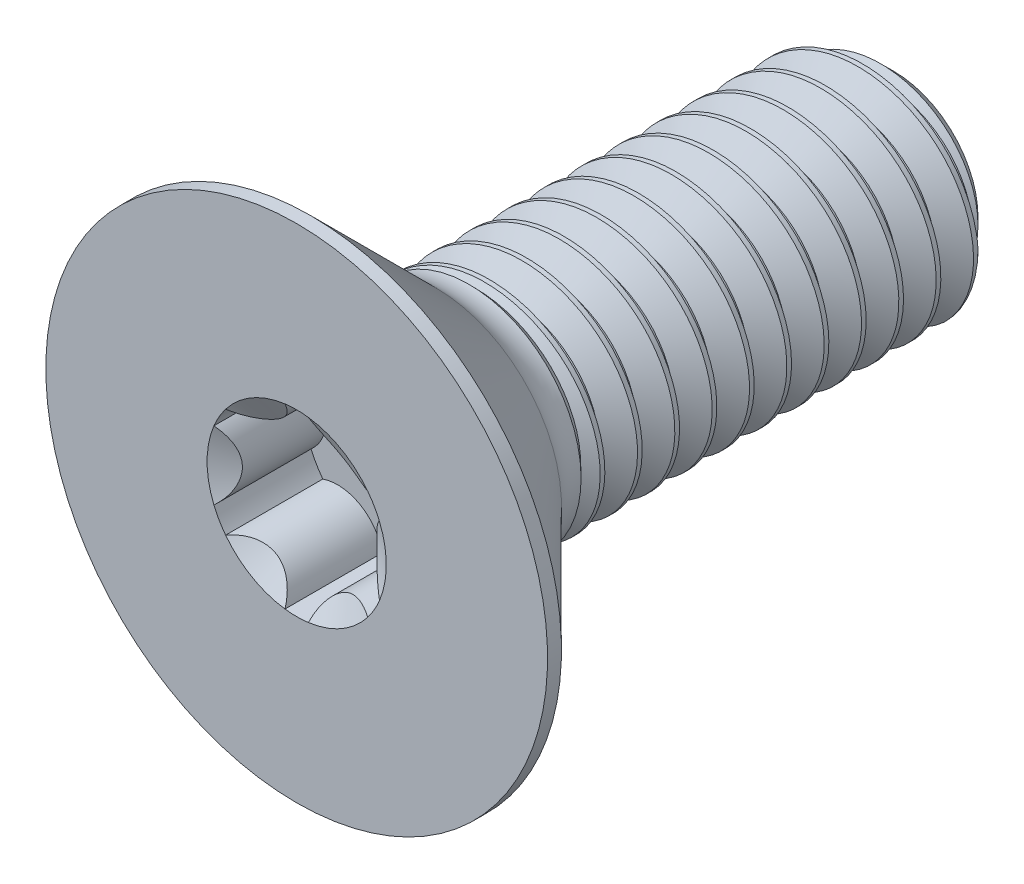
SolidWorks part; units mm, degrees
ref_plane "Front" through (0, 0, 0) normal (0, 0, 1) x (1, 0, 0)
ref_plane "Top" through (0, 0, 0) normal (0, 1, 0) x (1, 0, 0)
ref_plane "Right" through (0, 0, 0) normal (1, 0, 0) x (0, 0, -1)
sketch "Sketch1" plane through (0, 0, 0) normal (1, 0, 0) x (0, 0, -1)
  line L0 (0, 3.36) -> (0.186, 3.36) construction
  line L1 (0.186, 3.36) -> (1.86, 1.686) construction
  line L2 (0, 1.5) -> (8, 1.5)
  line L3 (8, 1.5) -> (8, 0)
  line L4 (8, 0) -> (0, 0)
  line L5 (0, 0) -> (0, 3.36) construction
  line L6 (0, 3.36) -> (0, -3.36) construction
  line L7 (8, 1.5) -> (8, -1.5) construction
  line L8 (0, -3.36) -> (0.186, -3.36) construction
  line L9 (0.186, -3.36) -> (1.86, -1.686) construction
  line L11 (0, 1.5) -> (0, 0)
  line L12 (2.309, 1.5) -> (2.309, 0) construction
  arc A1 (1.86, 1.686) -> (2.309, 1.5) centre (2.309, 2.135) ccw construction
  dimension "D1" = 0.186
revolve "Revolve1" add sketch "Sketch1" angle 360 mid plane about L4
sketch "Sketch3" plane through (0, 0, -8) normal (0, 0, -1) x (-1, 0, 0)
  circle A0 centre (0, 0) radius 1.5
curve "Helix/Spiral1" pitch 0.5 height 8 radius 1.5 centre (0, 0, -8) axis (0, 0, 1) start towards (0, 1, 0)
sketch "Sketch2" plane through (0, 0, 0) normal (1, 0, 0) x (0, 0, -1)
  line L0 (8, 1.5) -> (8.4375, 1.5)
  line L1 (8.4375, 1.5) -> (8.25, 1.1752)
  line L2 (8.25, 1.1752) -> (8.1875, 1.1752)
  line L3 (8.1875, 1.1752) -> (8, 1.5)
  line L4 (8.0938, 1.3376) -> (8.3438, 1.3376) construction
  dimension "D1" = 60
  dimension "D2" = 0.0625
  dimension "D3" = 0.25
chamfer "Chamfer1" distance 0.375 angle 45 1 edges at (0, 1.5, -8)
sweep "Cut-Sweep1" cut profiles "Sketch2" path "Helix/Spiral1" align with end faces yes
sketch "Sketch7" plane through (0, 0, 0) normal (1, 0, 0) x (0, 0, -1)
  line L0 (0, 3.36) -> (0.186, 3.36) construction
  line L1 (0.186, 3.36) -> (1.86, 1.686) construction
  line L2 (0, 3.36) -> (0.186, 3.36)
  line L3 (0.186, 3.36) -> (1.86, 1.686)
  line L4 (2.309, 1.5) -> (2.309, 0) construction
  line L5 (2.309, 1.5) -> (2.309, 0)
  line L7 (0, 0) -> (0, 3.36) construction
  line L8 (0, 0) -> (0, 3.36)
  line L9 (0, 0) -> (2.309, 0)
  line L10 (2.8355, 0) -> (-2.8355, 0) construction
  arc A0 (1.86, 1.686) -> (2.309, 1.5) centre (2.309, 2.135) ccw construction
  arc A1 (1.86, 1.686) -> (2.309, 1.5) centre (2.309, 2.135) ccw
revolve "Revolve2" add sketch "Sketch7" angle 360 mid plane about L9
ref_plane "Plane1" through (0, 0, -2.309) normal (0, 0, 1) x (1, 0, 0)
sketch "Sketch8" plane through (0, 0, -2.309) normal (0, 0, 1) x (1, 0, 0)
  circle A0 centre (0, 0) radius 1.5
extrude "Boss-Extrude1" add sketch "Sketch8" against normal through all draft 46
sketch "Sketch5" plane through (0, 0, 0) normal (0, 0, 1) x (1, 0, 0)
  line L0 (0, 0) -> (-1.2, 0) construction
  line L1 (0, 0) -> (-1.0392, 0.6) construction
  line L2 (0, 0) -> (-1.0392, -0.6) construction
  line L3 (-1.0392, -0.6) -> (0, 0)
  line L4 (0, 0) -> (-1.0392, 0.6)
  line L5 (0, 0) -> (-1.1087, -0.4592) construction
  line L6 (0, 1.2) -> (0, 1.05) construction
  line L7 (0, 1.05) -> (0, 0.9) construction
  circle A0 centre (0, 0) radius 1.2 construction
  circle A1 centre (0, 0) radius 1.05 construction
  circle A2 centre (0, 0) radius 0.9 construction
  arc A4 (-1.1087, -0.4592) -> (-1.1087, 0.4592) centre (-1.5097, 0) ccw
  arc A5 (-1.1087, 0.4592) -> (-1.0392, 0.6) centre (0, 0) cw
  arc A6 (-1.1087, -0.4592) -> (-1.0392, -0.6) centre (0, 0) ccw
  dimension "D3" = 1.8
  dimension "D4" = 30
  dimension "D5" = 30
  dimension "D1" = 7.5
extrude "Cut-Extrude2" cut sketch "Sketch5" against normal blind 1.302
pattern_circular "CirPattern1" count 6 over 360 of "Cut-Extrude2"
sketch "Sketch6" plane through (0, 0, 0) normal (0, 0, 1) x (1, 0, 0)
  circle A0 centre (0, 0) radius 1.2
extrude "Cut-Extrude3" cut sketch "Sketch6" against normal blind 1.302 draft 60
sketch "Sketch9" [suppressed] plane through (0, 0, -5.0772) normal (0, 0, 1) x (1, 0, 0)
  circle A1 centre (0, 0) radius 3.175
  circle A2 centre (0, 0) radius 3.175
  point P0 (0, 3.175)
  dimension "D1" = 0
extrude "Boss-Extrude2" [suppressed] add sketch "Sketch9" against normal offset from surface (13.9728 mm away) 22.225 up to face at (0, 1.125, -8)
sketch "Sketch10" plane through (0, 0, 0) normal (1, 0, 0) x (0, 0, -1)
  line L0 (8, 1.5) -> (8, -1.5) construction
  point P0 (7.25, -1.5)
  dimension "D1" = 0.75
equation "\"D3@Helix/Spiral1\" = \"Lg@Sketch1\""
equation "\"D2@Sketch2\" = \"D4@Helix/Spiral1\" * .125"
equation "\"D3@Sketch2\" = \"D4@Helix/Spiral1\" * .5"
equation "\"D1@Chamfer1\" = \"D4@Helix/Spiral1\" * .75"
equation "\"D1@Cut-Extrude2\" = \"Head Ht@Sketch1\" * .7"
equation "\"D1@Sketch1\" = \"Head Ht@Sketch1\" * .1"
equation "\"D1@Sketch10\" = \"D4@Helix/Spiral1\" * 1.5"
equation "\"D1@Cut-Extrude3\" = \"D1@Cut-Extrude2\""
equation "\"Torx Dia@Sketch5\" = \"Dia@Sketch1\" * .8"
equation "\"D3@Sketch5\" = \"Torx Dia@Sketch5\" * .75"
